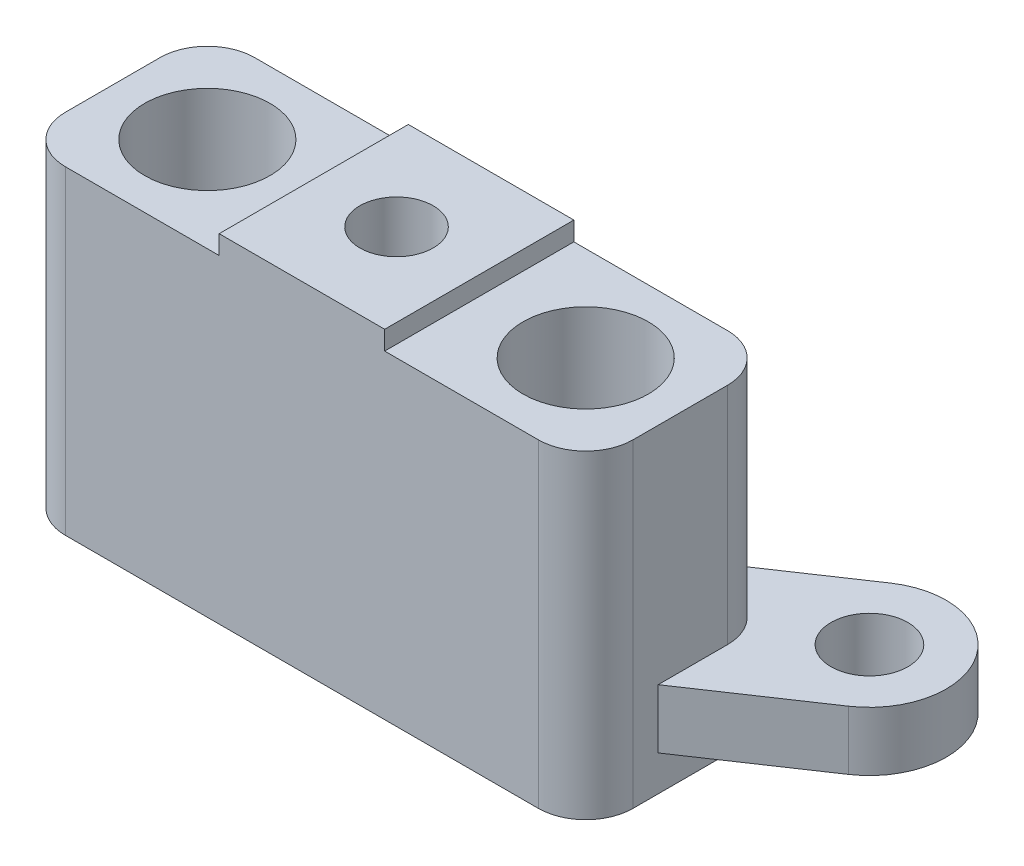
SolidWorks part; units mm, degrees
ref_plane "Front Plane" through (0, 0, 0) normal (0, 0, 1) x (1, 0, 0)
ref_plane "Top Plane" through (0, 0, 0) normal (0, 1, 0) x (1, 0, 0)
ref_plane "Right Plane" through (0, 0, 0) normal (1, 0, 0) x (0, 0, -1)
ref_axis "X-Axis" through (-88.4377, 0, 0) along (1, 0, 0)
ref_axis "Y-Axis" through (0, 0, -69.2525) along (0, 0, 1)
ref_axis "Z-Axis" through (0, -52.5493, 0) along (0, 1, 0)
sketch "Sketch25" plane through (0, 0, 0) normal (0, 1, 0) x (-1, 0, 0)
  line L8 (3.5, -4) -> (-3.5, -4)
  line L9 (3.5, -4) -> (3.5, 4)
  line L10 (3.5, 4) -> (-3.5, 4)
  line L11 (-3.5, -4) -> (-3.5, 4)
  line L12 (3.5, -4) -> (-3.5, 4) construction
  line L13 (3.5, 4) -> (-3.5, -4) construction
  point P8 (0, 0)
  dimension "D3" = 7
  dimension "D1" = 8
extrude "Boss-Extrude5" add sketch "Sketch25" along normal blind 12.8
sketch "Sketch26" plane through (0, 0, 0) normal (0, 1, 0) x (-1, 0, 0)
  line L0 (0, 4) -> (0, -4) construction
  line L1 (-12, -4) -> (12, -4)
  line L2 (-12, -4) -> (-12, 4)
  line L3 (-12, 4) -> (12, 4)
  line L4 (12, -4) -> (12, 4)
  line L5 (-12, 0) -> (12, 0) construction
  line L6 (-8, 0) -> (0, -4) construction
  line L7 (0, -4) -> (8, 0) construction
  line L10 (-3.5, -4) -> (3.5, -4) construction
  line L11 (3.5, 4) -> (-3.5, 4) construction
  circle A0 centre (-8, 0) radius 2.65
  circle A1 centre (8, 0) radius 2.65
  dimension "D2" = 5.3
  dimension "D1" = 24
  dimension "D3" = 16
extrude "Boss-Extrude6" add sketch "Sketch26" along normal blind 12
sketch "Sketch27" plane through (0, 12.8, 0) normal (0, 1, 0) x (1, 0, 0)
  circle A0 centre (0, 0) radius 1.55
  dimension "D1" = 3.1
extrude "Cut-Extrude1" cut sketch "Sketch27" against normal blind 6.5
ref_plane "Plane1" through (0, 0, 0) normal (0, -1, 0) x (-1, 0, 0)
sketch "Sketch29" plane through (0, 0, 0) normal (0, -1, 0) x (1, 0, 0)
  line L0 (0, 0) -> (0, 33) construction
  line L1 (0, 33) -> (-15, 33) construction
  line L2 (-15, 33) -> (-15, -5) construction
  line L3 (-16.8137, -2.3032) -> (-12, 0.9343)
  line L4 (-13.1863, -7.6968) -> (-7.6895, -4)
  line L5 (12, -4) -> (-12, -4) construction
  line L6 (-12, 0.9343) -> (-12, -4)
  line L7 (-12, -4) -> (-7.6895, -4)
  line L8 (16.8137, -2.3032) -> (12, 0.9343)
  line L9 (12, 0.9343) -> (12, -4)
  line L10 (12, -4) -> (7.6895, -4)
  line L11 (13.1863, -7.6968) -> (7.6895, -4)
  line L12 (-12, -4) -> (-12, 4) construction
  circle A0 centre (-15, -5) radius 1.625
  arc A1 (-16.8137, -2.3032) -> (-13.1863, -7.6968) centre (-15, -5) ccw
  circle A2 centre (15, -5) radius 1.625
  arc A3 (16.8137, -2.3032) -> (13.1863, -7.6968) centre (15, -5) cw
  point P9 (-12, 1.5774)
  point P21 (-12, 2.1169)
  point P24 (-12, 0.771)
  point P25 (-12, 1.9255)
  point P26 (-12, -4)
  point P28 (-12, 0.9343)
  dimension "D4" = 3.25
  dimension "D5" = 6.5
  dimension "D1" = 33
  dimension "D2" = 38
  dimension "D3" = 15
extrude "Boss-Extrude8" add sketch "Sketch29" against normal blind 2.5
sketch "Sketch31" plane through (0, 0, 0) normal (0, -1, 0) x (1, 0, 0)
  line L0 (7.6895, -4) -> (-7.6895, -4) construction
  line L1 (-12, 4) -> (12, 4)
  line L2 (-12, 4) -> (-12, -4)
  line L3 (-12, -4) -> (12, -4)
  line L4 (12, 4) -> (12, -4)
  line L5 (12, 4) -> (12, 0.9343) construction
extrude "Boss-Extrude9" add sketch "Sketch31" along normal blind 1.5
fillet "Fillet1" radius 2 6 edges at (-12, 5.25, 4) (12, 5.25, 4) (-12, -0.75, -4) (12, -0.75, -4) (-12, 7.25, -4) (12, 7.25, -4)
